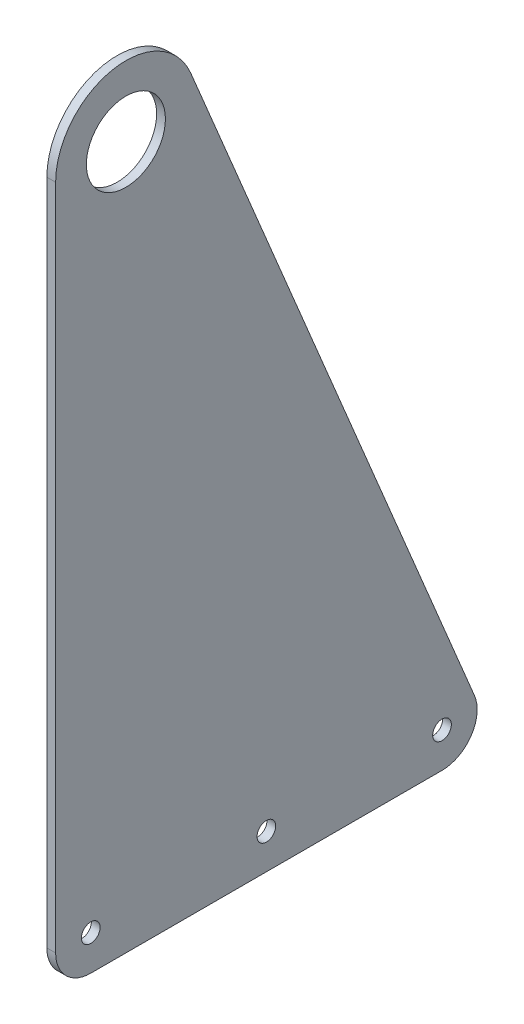
SolidWorks part; units mm, degrees
material "6061 Alloy"
ref_plane "Front" through (0, 0, 0) normal (0, 0, 1) x (1, 0, 0)
ref_plane "Top" through (0, 0, 0) normal (0, 1, 0) x (1, 0, 0)
ref_plane "Right" through (0, 0, 0) normal (1, 0, 0) x (0, 0, -1)
sketch "Sketch1" plane through (0, 0, 0) normal (1, 0, 0) x (0, 0, -1)
  line L0 (-12.7, -241.3) -> (114.3, -241.3) construction
  line L1 (-25.4, -241.3) -> (-25.4, 0)
  line L2 (23.4462, 9.7692) -> (126.0231, -236.4154)
  line L3 (114.3, -254) -> (-12.7, -254)
  circle A0 centre (0, 0) radius 14.2875
  arc A1 (23.4462, 9.7692) -> (-25.4, 0) centre (0, 0) ccw
  arc A2 (-25.4, -241.3) -> (-12.7, -254) centre (-12.7, -241.3) ccw
  arc A3 (114.3, -254) -> (126.0231, -236.4154) centre (114.3, -241.3) ccw
  circle A4 centre (-12.7, -241.3) radius 3.3782
  circle A5 centre (50.8, -241.3) radius 3.3782
  circle A6 centre (114.3, -241.3) radius 3.3782
  point P3 (50.4326, -241.3)
  point P12 (50.8, -241.3)
  dimension "D1" = 28.575
  dimension "D2" = 50.8
  dimension "D3" = 6.7564
  dimension "D6" = 12.7
  dimension "D4" = 254
  dimension "D5" = 127
extrude "Boss-Extrude1" add sketch "Sketch1" along normal blind 3.175
sketch "Sketch2" [suppressed] plane through (3.175, 0, 0) normal (1, 0, 0) x (0, 0, -1)
  line L0 (-17.9605, -94.1605) -> (17.9605, -58.2395) construction
  line L1 (-17.9605, -58.2395) -> (17.9605, -94.1605) construction
  line L2 (-17.9605, -58.2395) -> (-17.9605, -94.1605) construction
  line L3 (-17.9605, -94.1605) -> (17.9605, -94.1605) construction
  circle A0 centre (-17.9605, -58.2395) radius 3.3782
  circle A1 centre (17.9605, -58.2395) radius 2.3812
  circle A2 centre (17.9605, -94.1605) radius 3.3782
  circle A3 centre (-17.9605, -94.1605) radius 2.3812
  circle A4 centre (0, -76.2) radius 19.05
  circle A5 centre (0, 0) radius 14.2875 construction
  point P14 (0, -76.2)
  point P18 (0, -76.2)
  dimension "D2" = 4.7625
  dimension "D3" = 6.7564
  dimension "D4" = 38.1
  dimension "D5" = 76.2
  dimension "D1" = 50.8
extrude "Cut-Extrude1" [suppressed] cut sketch "Sketch2" against normal through all
sketch "Sketch3" [suppressed] plane through (3.175, 0, 0) normal (1, 0, 0) x (0, 0, -1)
  circle A0 centre (0, -76.2) radius 30.1625
  circle A1 centre (0, 0) radius 14.2875 construction
  dimension "D1" = 60.325
  dimension "D2" = 76.2
extrude "Cut-Extrude2" [suppressed] cut sketch "Sketch3" against normal through all
